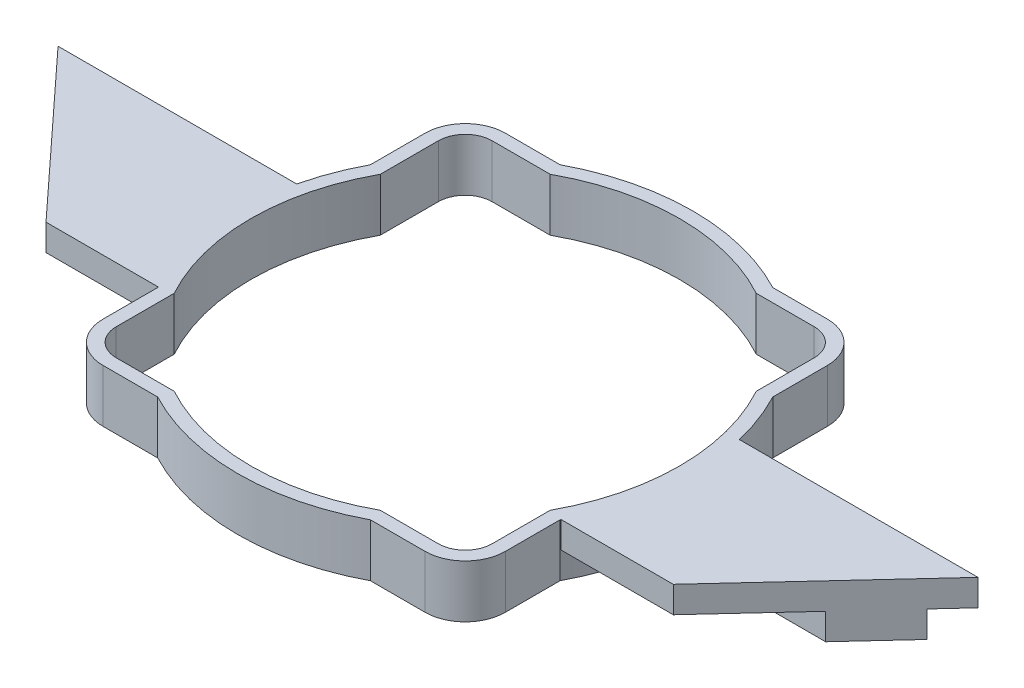
SolidWorks part; units mm, degrees
ref_plane "Front Plane" through (0, 0, 0) normal (0, 0, 1) x (1, 0, 0)
ref_plane "Top Plane" through (0, 0, 0) normal (0, 1, 0) x (1, 0, 0)
ref_plane "Right Plane" through (0, 0, 0) normal (1, 0, 0) x (0, 0, -1)
sketch "Sketch1" plane through (0, 0, 0) normal (0, 1, 0) x (1, 0, 0)
  line L1 (-127, -76.2) -> (127, -76.2)
  line L2 (-127, -76.2) -> (-127, 76.2)
  line L3 (-127, 76.2) -> (127, 76.2)
  line L4 (127, -76.2) -> (127, 76.2)
  line L5 (-127, -76.2) -> (127, 76.2) construction
  line L6 (-127, 76.2) -> (127, -76.2) construction
  point P0 (0, 0)
  dimension "D1" = 254
  dimension "D2" = 152.4
extrude "Boss-Extrude1" add sketch "Sketch1" along normal blind 12.7 contours L2 L3 L4 L1
sketch "Sketch4" plane through (0, 0, 0) normal (0, -1, 0) x (1, 0, 0)
  line L0 (45.212, 24.7894) -> (45.212, 38.735)
  line L1 (38.735, 45.212) -> (24.7894, 45.212)
  line L2 (-24.7894, 45.212) -> (-38.735, 45.212)
  line L3 (-45.212, 38.735) -> (-45.212, 24.7894)
  line L4 (-45.212, -24.7894) -> (-45.212, -38.735)
  line L5 (-38.735, -45.212) -> (-24.7894, -45.212)
  line L6 (24.7894, -45.212) -> (38.735, -45.212)
  line L7 (45.212, -38.735) -> (45.212, -24.7894)
  line L9 (45.085, 24.7569) -> (45.085, 38.735)
  line L10 (38.735, 45.085) -> (24.7569, 45.085)
  line L11 (-24.7569, 45.085) -> (-38.735, 45.085)
  line L12 (-45.085, 38.735) -> (-45.085, 24.7569)
  line L13 (-45.085, -24.7569) -> (-45.085, -38.735)
  line L14 (-38.735, -45.085) -> (-24.7569, -45.085)
  line L15 (24.7569, -45.085) -> (38.735, -45.085)
  line L24 (45.085, -38.735) -> (45.085, -24.7569)
  line L25 (45.085, 24.7569) -> (45.085, 38.735) construction
  line L26 (38.735, 45.085) -> (24.7569, 45.085) construction
  line L27 (-24.7569, 45.085) -> (-38.735, 45.085) construction
  line L28 (-45.085, 38.735) -> (-45.085, 24.7569) construction
  line L29 (-45.085, -24.7569) -> (-45.085, -38.735) construction
  line L30 (-38.735, -45.085) -> (-24.7569, -45.085) construction
  line L31 (24.7569, -45.085) -> (38.735, -45.085) construction
  line L32 (45.085, -38.735) -> (45.085, -24.7569) construction
  line L33 (48.387, 25.5898) -> (48.387, 38.735)
  line L34 (38.735, 48.387) -> (25.5898, 48.387)
  line L35 (-25.5898, 48.387) -> (-38.735, 48.387)
  line L36 (-48.387, 38.735) -> (-48.387, 25.5898)
  line L37 (-48.387, -25.5898) -> (-48.387, -38.735)
  line L38 (-38.735, -48.387) -> (-25.5898, -48.387)
  line L39 (25.5898, -48.387) -> (38.735, -48.387)
  line L40 (48.387, -38.735) -> (48.387, -25.5898)
  arc A0 (45.212, 38.735) -> (38.735, 45.212) centre (38.735, 38.735) ccw
  arc A1 (24.7894, 45.212) -> (-24.7894, 45.212) centre (0, 0) ccw
  arc A2 (-38.735, 45.212) -> (-45.212, 38.735) centre (-38.735, 38.735) ccw
  arc A3 (-45.212, 24.7894) -> (-45.212, -24.7894) centre (0, 0) ccw
  arc A4 (-45.212, -38.735) -> (-38.735, -45.212) centre (-38.735, -38.735) ccw
  arc A5 (-24.7894, -45.212) -> (24.7894, -45.212) centre (0, 0) ccw
  arc A6 (38.735, -45.212) -> (45.212, -38.735) centre (38.735, -38.735) ccw
  arc A7 (45.212, -24.7894) -> (45.212, 24.7894) centre (0, 0) ccw
  arc A24 (45.085, 38.735) -> (38.735, 45.085) centre (38.735, 38.735) ccw
  arc A25 (24.7569, 45.085) -> (-24.7569, 45.085) centre (0, 0) ccw
  arc A26 (-38.735, 45.085) -> (-45.085, 38.735) centre (-38.735, 38.735) ccw
  arc A27 (-45.085, 24.7569) -> (-45.085, -24.7569) centre (0, 0) ccw
  arc A28 (-45.085, -38.735) -> (-38.735, -45.085) centre (-38.735, -38.735) ccw
  arc A29 (-24.7569, -45.085) -> (24.7569, -45.085) centre (0, 0) ccw
  arc A30 (38.735, -45.085) -> (45.085, -38.735) centre (38.735, -38.735) ccw
  arc A31 (45.085, -24.7569) -> (45.085, 24.7569) centre (0, 0) ccw
  arc A32 (45.085, 38.735) -> (38.735, 45.085) centre (38.735, 38.735) ccw construction
  arc A33 (24.7569, 45.085) -> (-24.7569, 45.085) centre (0, 0) ccw construction
  arc A34 (-38.735, 45.085) -> (-45.085, 38.735) centre (-38.735, 38.735) ccw construction
  arc A35 (-45.085, 24.7569) -> (-45.085, -24.7569) centre (0, 0) ccw construction
  arc A36 (-45.085, -38.735) -> (-38.735, -45.085) centre (-38.735, -38.735) ccw construction
  arc A37 (-24.7569, -45.085) -> (24.7569, -45.085) centre (0, 0) ccw construction
  arc A38 (38.735, -45.085) -> (45.085, -38.735) centre (38.735, -38.735) ccw construction
  arc A39 (45.085, -24.7569) -> (45.085, 24.7569) centre (0, 0) ccw construction
  arc A40 (48.387, 38.735) -> (38.735, 48.387) centre (38.735, 38.735) ccw
  arc A41 (25.5898, 48.387) -> (-25.5898, 48.387) centre (0, 0) ccw
  arc A42 (-38.735, 48.387) -> (-48.387, 38.735) centre (-38.735, 38.735) ccw
  arc A43 (-48.387, 25.5898) -> (-48.387, -25.5898) centre (0, 0) ccw
  arc A44 (-48.387, -38.735) -> (-38.735, -48.387) centre (-38.735, -38.735) ccw
  arc A45 (-25.5898, -48.387) -> (25.5898, -48.387) centre (0, 0) ccw
  arc A46 (38.735, -48.387) -> (48.387, -38.735) centre (38.735, -38.735) ccw
  arc A47 (48.387, -25.5898) -> (48.387, 25.5898) centre (0, 0) ccw
  dimension "D1" = 0
  dimension "D2" = 0.127
  dimension "D3" = 3.175
extrude "Cut-Extrude1" cut sketch "Sketch4" against normal through all flip side to cut
sketch "Sketch5" plane through (0, 0, 0) normal (0, 1, 0) x (1, 0, 0)
  line L0 (54.3674, 6.35) -> (104.775, 6.35)
  line L1 (104.775, 6.35) -> (93.0414, -6.35)
  line L2 (93.0414, -6.35) -> (54.3674, -6.35)
  line L3 (0, 0) -> (0, 33.5108) construction
  line L4 (-93.0414, -6.35) -> (-54.3674, -6.35)
  line L5 (-104.775, 6.35) -> (-93.0414, -6.35)
  line L6 (-54.3674, 6.35) -> (-104.775, 6.35)
  arc A0 (48.387, -25.5898) -> (48.387, 25.5898) centre (0, 0) ccw construction
  arc A1 (54.3674, -6.35) -> (54.3674, 6.35) centre (0, 0) ccw
  arc A2 (-54.3674, -6.35) -> (-54.3674, 6.35) centre (0, 0) cw
  point P9 (98.9082, 0)
  dimension "D1" = 12.7
  dimension "D2" = 104.775
extrude "Boss-Extrude2" add sketch "Sketch5" along normal blind 6.35
sketch "Sketch6" plane through (0, 0, 0) normal (0, 1, 0) x (1, 0, 0)
  line L0 (53.2433, 12.7) -> (110.6418, 12.7)
  line L1 (110.6418, 12.7) -> (75.4411, -25.4)
  line L2 (75.4411, -25.4) -> (48.4869, -25.4)
  line L3 (93.0414, -6.35) -> (104.775, 6.35) construction
  line L4 (104.775, 6.35) -> (54.3674, 6.35) construction
  line L5 (54.3674, -6.35) -> (93.0414, -6.35) construction
  line L6 (0, 0) -> (0, 23.3719) construction
  line L7 (-75.4411, -25.4) -> (-48.4869, -25.4)
  line L8 (-110.6418, 12.7) -> (-75.4411, -25.4)
  line L9 (-53.2433, 12.7) -> (-110.6418, 12.7)
  arc A0 (48.387, -25.5898) -> (48.387, 25.5898) centre (0, 0) ccw construction
  arc A1 (48.4869, -25.4) -> (53.2433, 12.7) centre (0, 0) ccw
  arc A2 (-48.4869, -25.4) -> (-53.2433, 12.7) centre (0, 0) cw
  dimension "D1" = 6.35
  dimension "D2" = 19.05
extrude "Boss-Extrude3" add sketch "Sketch6" along normal blind 6.35 from surface starting at face at (76.7302, 6.35, 0)
